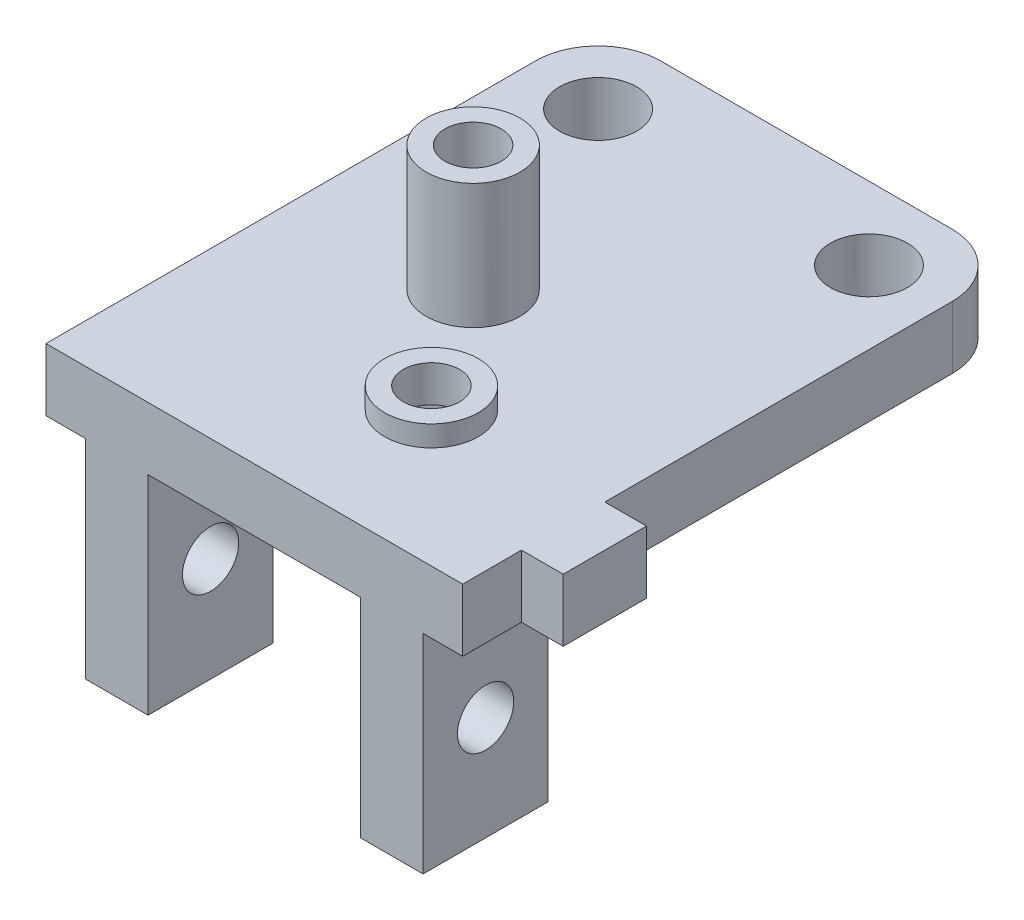
SolidWorks part; units mm, degrees
ref_plane "Front Plane" through (0, 0, 0) normal (0, 0, 1) x (1, 0, 0)
ref_plane "Top Plane" through (0, 0, 0) normal (0, 1, 0) x (1, 0, 0)
ref_plane "Right Plane" through (0, 0, 0) normal (1, 0, 0) x (0, 0, -1)
sketch "Sketch1" plane through (0, 0, 0) normal (0, 1, 0) x (1, 0, 0)
  line L0 (40, 5.65) -> (40, 0)
  line L1 (0, 53) -> (40, 53)
  line L2 (0, 53) -> (0, 0)
  line L3 (0, 0) -> (40, 0)
  line L4 (40, 53) -> (40, 13.65)
  line L5 (40, 13.65) -> (44, 13.65)
  line L7 (40, 5.65) -> (44, 5.65)
  line L8 (44, 13.65) -> (44, 5.65)
  line L9 (20, 53) -> (20, 0) construction
  point P4 (7, 46)
  point P5 (0, 0)
  point P7 (24, 13)
  point P9 (16, 25)
  dimension "D1" = 40
  dimension "D3" = 7
  dimension "D4" = 7
  dimension "D8" = 13
  dimension "D10" = 4
  dimension "D11" = 8
  dimension "D12" = 5.65
  dimension "D5" = 4
  dimension "D6" = 4
  dimension "D7" = 25
  dimension "D2" = 21
extrude "Boss-Extrude1" add sketch "Sketch1" along normal blind 6 contours L2 L3 L0 L7 L8 L5 L4 L1
ref_plane "Plane1" through (20, 0, 0) normal (1, 0, 0) x (0, 0, -1)
sketch "Sketch16" plane through (0, 6, 0) normal (0, 1, 0) x (1, 0, 0)
  circle A0 centre (24, 13) radius 4.5
  circle A1 centre (16, 25) radius 4.5
  dimension "D1" = 9
extrude "Boss-Extrude3" add sketch "Sketch16" along normal blind 12 contours A1
extrude "Boss-Extrude4" add sketch "Sketch16<3>" along normal blind 2 contours A0
sketch "Sketch16<3>" plane through (0, 6, 0) normal (0, 1, 0) x (1, 0, 0) same geometry as "Sketch16"
sketch "Sketch12" plane through (0, 0, 0) normal (0, -1, 0) x (1, 0, 0)
  line L1 (28.2, -10.5751) -> (24, -8.1503)
  line L2 (24, -8.1503) -> (19.8, -10.5751)
  line L3 (19.8, -10.5751) -> (19.8, -15.4249)
  line L4 (19.8, -15.4249) -> (24, -17.8497)
  line L5 (24, -17.8497) -> (28.2, -15.4249)
  line L6 (28.2, -15.4249) -> (28.2, -10.5751)
  line L7 (16, -20.1503) -> (11.8, -22.5751)
  line L8 (11.8, -22.5751) -> (11.8, -27.4249)
  line L9 (11.8, -27.4249) -> (16, -29.8497)
  line L10 (16, -29.8497) -> (20.2, -27.4249)
  line L11 (20.2, -27.4249) -> (20.2, -22.5751)
  line L12 (20.2, -22.5751) -> (16, -20.1503)
  circle A0 centre (24, -13) radius 4.2 construction
  circle A1 centre (16, -25) radius 4.2 construction
  dimension "D1" = 8.4
  dimension "D2" = 8.4
extrude "Cut-Extrude1" cut sketch "Sketch12" against normal blind 4.5
hole_wizard "Ø5.4mm Dowel Hole1" positions "Sketch18" profile "Sketch19" hole size "Ø5.0" standard "ANSI Metric" end condition through all
sketch "Sketch18" plane through (0, 0, 0) normal (0, -1, 0) x (-1, 0, 0)
  point P0 (-16, 25)
  point P3 (-24, 13)
sketch "Sketch19" plane through (16, 0, -25) normal (1, 0, 0) x (0, 0, -1)
  line L0 (0, 0) -> (0, 18)
  line L1 (0, 18) -> (2.7, 18)
  line L2 (2.7, 18) -> (2.7, 0)
  line L5 (2.7, 0) -> (0, 0)
  line L11 (0, -6.35) -> (0, 107.95) construction
  dimension "Thru Hole Dia." = 5.4
  dimension "Thru Hole Depth" = 18
hole_wizard "Ø7.4mm Dowel Hole2" positions "Sketch13" profile "Sketch14" hole size "Ø5.0" standard "ANSI Metric" end condition through all
sketch "Sketch13" plane through (0, 6, 0) normal (0, 1, 0) x (1, 0, 0)
  point P0 (7, 46)
sketch "Sketch14" plane through (7, 6, -46) normal (1, 0, 0) x (0, 0, 1)
  line L0 (0, 0) -> (0, 6)
  line L1 (0, 6) -> (3.7, 6)
  line L2 (3.7, 6) -> (3.7, 0)
  line L5 (3.7, 0) -> (0, 0)
  line L11 (0, -6.35) -> (0, 107.95) construction
  dimension "Thru Hole Dia." = 7.4
  dimension "Thru Hole Depth" = 6
sketch "Sketch2" plane through (0, 0, 0) normal (0, -1, 0) x (1, 0, 0)
  line L0 (0, 0) -> (40, 0) construction
  line L1 (9.8, 0) -> (3.8, 0)
  line L2 (9.8, 0) -> (9.8, -12)
  line L3 (9.8, -12) -> (3.8, -12)
  line L4 (3.8, 0) -> (3.8, -12)
  line L6 (0, -53) -> (0, 0) construction
  dimension "D1" = 12
  dimension "D2" = 6
  dimension "D3" = 3.8
extrude "Boss-Extrude2" add sketch "Sketch2" along normal blind 20
hole_wizard "Ø5.4mm Dowel Hole3" positions "Sketch8" profile "Sketch9" hole size "Ø5.0" standard "ANSI Metric" end condition through all
sketch "Sketch8" plane through (9.8, 0, 0) normal (1, 0, 0) x (0, 0, -1)
  line L0 (12, -20) -> (12, 0) construction
  line L1 (12, -20) -> (0, -20) construction
  point P0 (6, -10)
  dimension "D1" = 6
  dimension "D2" = 10
sketch "Sketch9" plane through (9.8, -10, -6) normal (0, 1, 0) x (0, 0, -1)
  line L0 (0, 0) -> (0, 9.8)
  line L1 (0, 9.8) -> (2.7, 9.8)
  line L2 (2.7, 9.8) -> (2.7, 0)
  line L5 (2.7, 0) -> (0, 0)
  line L11 (0, -6.35) -> (0, 107.95) construction
  dimension "Thru Hole Dia." = 5.4
  dimension "Thru Hole Depth" = 9.8
mirror "Mirror1" about plane through (20, 0, 0) normal (1, 0, 0) of "Ø7.4mm Dowel Hole2", "Ø5.4mm Dowel Hole3", "Boss-Extrude2"
fillet "Fillet1" radius 6 2 edges at (0, 3, -53) (40, 3, -53)
equation "\"D6@Sketch1\"=\"D5@Sketch1\""
equation "\"D2@Sketch12\"=\"D1@Sketch12\""
